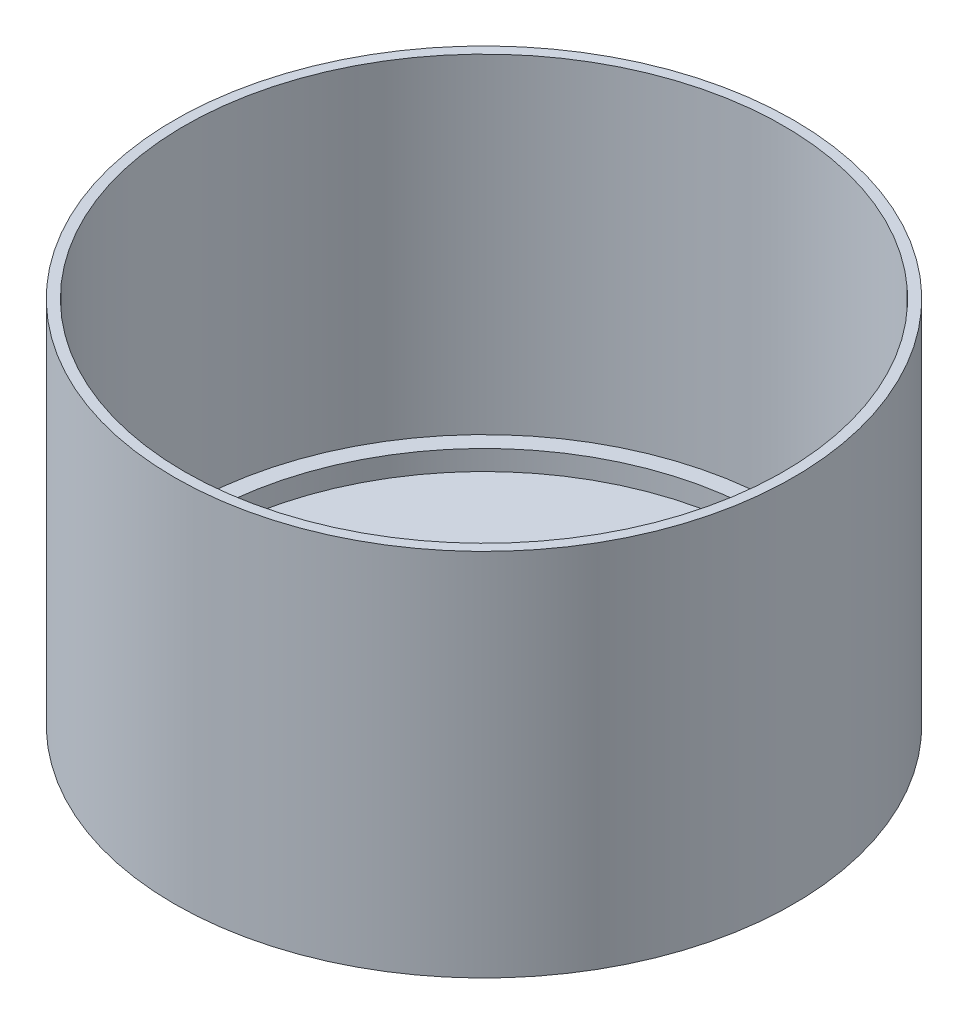
SolidWorks part; units mm, degrees
ref_plane "Alzado" through (0, 0, 0) normal (0, 0, 1) x (1, 0, 0)
ref_plane "Planta" through (0, 0, 0) normal (0, 1, 0) x (1, 0, 0)
ref_plane "Vista lateral" through (0, 0, 0) normal (1, 0, 0) x (0, 0, -1)
sketch "Sketch1" plane through (0, 0, 0) normal (0, 1, 0) x (1, 0, 0)
  circle A2 centre (0, 0) radius 30
  circle A3 centre (0, 0) radius 31
  dimension "D1" = 60
  dimension "D2" = 62
extrude "Boss-Extrude1" add sketch "Sketch1" along normal blind 37
sketch "Sketch2" plane through (0, 0, 0) normal (0, 1, 0) x (1, 0, 0)
  circle A0 centre (0, 0) radius 31
extrude "Boss-Extrude2" add sketch "Sketch2" along normal blind 2
sketch "Sketch5" plane through (0, 2, 0) normal (0, 1, 0) x (1, 0, 0)
  circle A0 centre (0, 0) radius 30
  circle A1 centre (0, 0) radius 28.3
  dimension "5.7" = 1.7
extrude "Boss-Extrude4" add sketch "Sketch5" along normal blind 2
sketch "Sketch6" plane through (0, 2, 0) normal (0, 1, 0) x (1, 0, 0)
  circle A0 centre (0, 0) radius 4
  dimension "D1" = 8
extrude "Cut-Extrude1" cut sketch "Sketch6" against normal blind 2
